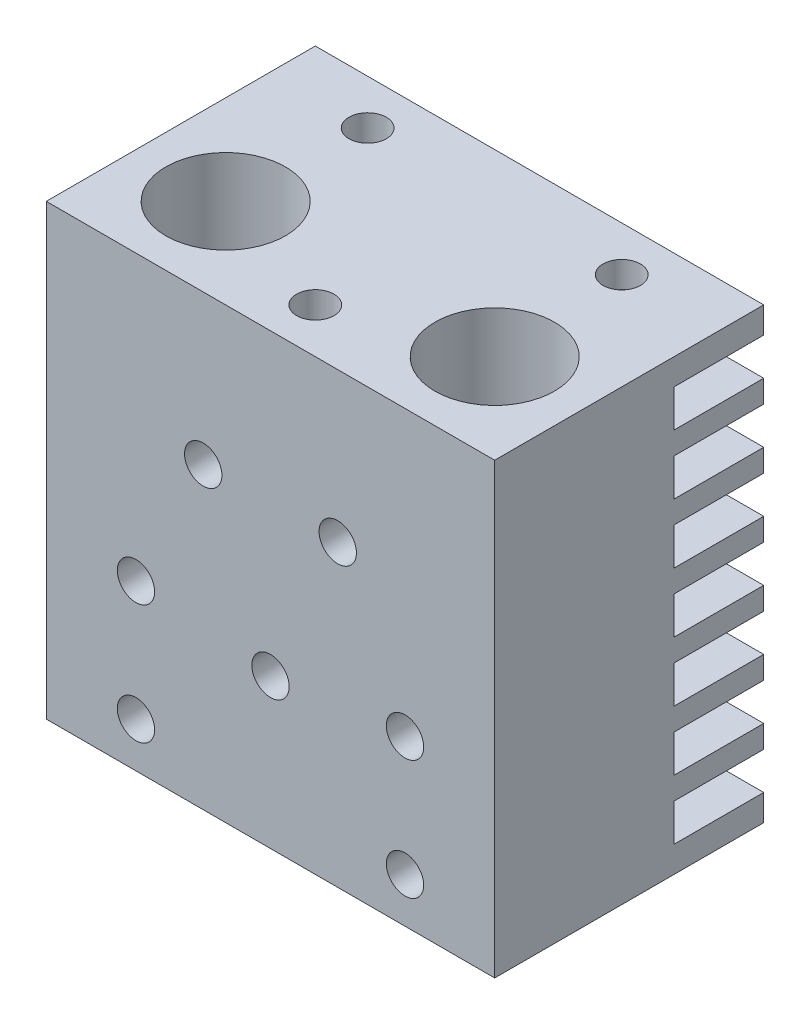
SolidWorks part; units mm, degrees
material "6061-T6 (SS)"
ref_plane "Front Plane" through (0, 0, 0) normal (0, 0, 1) x (1, 0, 0)
ref_plane "Top Plane" through (0, 0, 0) normal (0, 1, 0) x (1, 0, 0)
ref_plane "Right Plane" through (0, 0, 0) normal (1, 0, 0) x (0, 0, -1)
sketch "Sketch1" plane through (0, 0, 0) normal (0, 1, 0) x (1, 0, 0)
  line L1 (15, 9) -> (-15, 9)
  line L2 (15, 9) -> (15, -9)
  line L3 (15, -9) -> (-15, -9)
  line L4 (-15, 9) -> (-15, -9)
  line L5 (15, 9) -> (-15, -9) construction
  line L6 (15, -9) -> (-15, 9) construction
  point P0 (0, 0)
  dimension "D1" = 18
  dimension "D2" = 30
extrude "Boss-Extrude1" add sketch "Sketch1" along normal blind 30
sketch "Sketch2" plane through (0, 30, 0) normal (0, 1, 0) x (1, 0, 0)
  line L0 (-15, 6) -> (15, 6) construction
  line L1 (-15, 9) -> (-15, -9) construction
  line L2 (15, -9) -> (15, 9) construction
  line L3 (-15, -9) -> (15, -9) construction
  line L4 (-15, -6) -> (15, -6) construction
  line L5 (-15, -3) -> (15, -3) construction
  circle A0 centre (0, -6) radius 1.25
  circle A1 centre (-8.5, 6) radius 1.25
  circle A2 centre (8.5, 6) radius 1.25
  dimension "D3" = 2.5
  dimension "D4" = 23.5
  dimension "D5" = 6.5
  dimension "D6" = 2.5
  dimension "D7" = 2.5
  dimension "D1" = 15
  dimension "D2" = 3
  dimension "D8" = 6
extrude "Cut-Extrude1" cut sketch "Sketch2" against normal blind 8
sketch "Sketch3" plane through (0, 30, 0) normal (0, 1, 0) x (1, 0, 0)
  line L0 (-9, -3) -> (9, -3) construction
  line L1 (-15, -9) -> (15, -9) construction
  line L2 (15, -9) -> (15, 9) construction
  circle A0 centre (-9, -3) radius 4
  circle A1 centre (9, -3) radius 4
  dimension "D2" = 8
  dimension "D3" = 8
  dimension "D1" = 6
  dimension "D4" = 6
  dimension "D5" = 18
extrude "Cut-Extrude2" cut sketch "Sketch3" against normal blind 6.5
sketch "Sketch4" plane through (0, 23.5, 0) normal (0, 1, 0) x (1, 0, 0)
  circle A0 centre (9, -3) radius 2.1
  circle A1 centre (-9, -3) radius 2.1
  dimension "D1" = 4.2
  dimension "D2" = 4.2
extrude "Cut-Extrude3" cut sketch "Sketch4" against normal through all
sketch "Sketch5" plane through (15, 0, 0) normal (1, 0, 0) x (0, 0, -1)
  line L0 (9, 30) -> (9, 0) construction
  line L1 (3, 8.25) -> (15, 8.25)
  line L2 (15, 8.25) -> (15, 5.75)
  line L3 (3, 5.75) -> (15, 5.75)
  line L4 (3, 8.25) -> (3, 5.75)
  line L5 (3, 12.25) -> (15, 12.25)
  line L6 (15, 12.25) -> (15, 9.75)
  line L7 (-9, 0) -> (9, 0) construction
  line L8 (3, 9.75) -> (15, 9.75)
  line L9 (3, 12.25) -> (3, 9.75)
  line L10 (3, 16.25) -> (15, 16.25)
  line L11 (15, 16.25) -> (15, 13.75)
  line L12 (3, 13.75) -> (15, 13.75)
  line L13 (3, 16.25) -> (3, 13.75)
  line L14 (3, 20.25) -> (15, 20.25)
  line L15 (15, 20.25) -> (15, 17.75)
  line L16 (3, 17.75) -> (15, 17.75)
  line L17 (3, 20.25) -> (3, 17.75)
  line L18 (3, 24.25) -> (15, 24.25)
  line L19 (15, 24.25) -> (15, 21.75)
  line L20 (3, 21.75) -> (15, 21.75)
  line L21 (3, 24.25) -> (3, 21.75)
  line L22 (3, 28.25) -> (15, 28.25)
  line L23 (15, 28.25) -> (15, 25.75)
  line L24 (3, 25.75) -> (15, 25.75)
  line L25 (3, 28.25) -> (3, 25.75)
  line L26 (-9, 30) -> (9, 30) construction
  line L38 (3, 4.25) -> (15, 4.25)
  line L39 (3, 4.25) -> (3, 1.75)
  line L40 (3, 1.75) -> (15, 1.75)
  line L41 (15, 4.25) -> (15, 1.75)
  line L42 (3, 4.25) -> (15, 1.75) construction
  line L43 (3, 1.75) -> (15, 4.25) construction
  point P32 (9, 3)
  dimension "D1" = 2.5
  dimension "D2" = 1.75
  dimension "D3" = 6
  dimension "D5" = 1.75
  dimension "D4" = 7
extrude "Cut-Extrude4" cut sketch "Sketch5" against normal up to next
sketch "Sketch6" plane through (0, 0, 0) normal (0, -1, 0) x (1, 0, 0)
  circle A0 centre (9, 3) radius 3.45
  circle A1 centre (-9, 3) radius 3.45
  dimension "D1" = 6.9
  dimension "D2" = 6.9
extrude "Cut-Extrude5" cut sketch "Sketch6" against normal blind 14
sketch "Sketch7" plane through (0, 0, 9) normal (0, 0, 1) x (1, 0, 0)
  line L0 (9, 30) -> (9, 0) construction
  line L1 (-15, 30) -> (15, 30) construction
  line L2 (-15, 0) -> (15, 0) construction
  line L3 (15, 30) -> (15, 0) construction
  line L4 (-9, 30) -> (-9, 0) construction
  line L5 (-15, 3) -> (15, 3) construction
  line L6 (-15, 30) -> (-15, 0) construction
  line L7 (15, 11) -> (-15, 11) construction
  line L8 (0, 0) -> (0, 30) construction
  line L9 (-15, 20) -> (15, 20) construction
  circle A0 centre (-4.5, 20) radius 1.25
  circle A1 centre (4.5, 20) radius 1.25
  circle A2 centre (-9, 11) radius 1.25
  circle A3 centre (-9, 3) radius 1.25
  circle A4 centre (9, 11) radius 1.25
  circle A5 centre (9, 3) radius 1.25
  circle A6 centre (0, 10) radius 1.25
  dimension "D1" = 2.5
  dimension "D2" = 2.5
  dimension "D3" = 2.5
  dimension "D4" = 2.5
  dimension "D5" = 2.5
  dimension "D6" = 2.5
  dimension "D7" = 2.5
  dimension "D15" = 19.5
  dimension "D8" = 6
  dimension "D9" = 18
  dimension "D10" = 3
  dimension "D11" = 11
  dimension "D12" = 10
  dimension "D13" = 20
  dimension "D14" = 10.5
extrude "Cut-Extrude6" cut sketch "Sketch7" against normal through all
chamfer "Chamfer1" distance 1.7 angle 21 2 edges at (-9, 23.5, 5.1) (9, 23.5, 5.1) first distance on face at (-9, 23.5, 5.1) first distance on face at (9, 23.5, 5.1)
